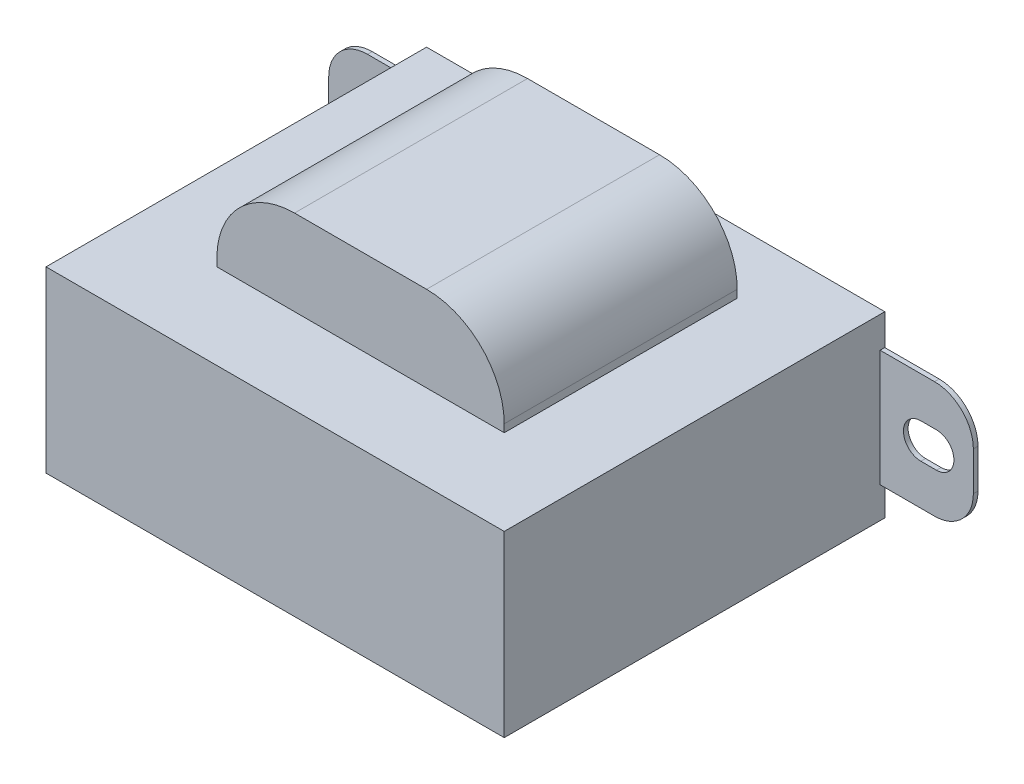
SolidWorks part; units mm, degrees
ref_plane "前视基准面" through (0, 0, 0) normal (0, 0, 1) x (1, 0, 0)
ref_plane "上视基准面" through (0, 0, 0) normal (0, 1, 0) x (1, 0, 0)
ref_plane "右视基准面" through (0, 0, 0) normal (1, 0, 0) x (0, 0, -1)
sketch "草图1" plane through (0, 0, 0) normal (0, 0, 1) x (1, 0, 0)
  line L0 (0, 78.0676) -> (0, -98.3955) construction
  line L1 (-29.5, 11.5) -> (29.5, 11.5)
  line L2 (-29.5, 11.5) -> (-29.5, -11.5)
  line L3 (-29.5, -11.5) -> (29.5, -11.5)
  line L4 (29.5, 11.5) -> (29.5, -11.5)
  line L5 (-98.6118, 0) -> (97.7467, 0) construction
  dimension "D1" = 23
  dimension "D2" = 59
extrude "拉伸1" add sketch "草图1" along normal blind 49
sketch "草图2" plane through (0, 0, 49) normal (0, 0, 1) x (1, 0, 0)
  line L1 (-8.5, 22.5) -> (8.5, 22.5)
  line L2 (-18.5, 12.5) -> (-18.5, -12.5)
  line L3 (-8.5, -22.5) -> (8.5, -22.5)
  line L4 (18.5, 12.5) -> (18.5, -12.5)
  arc A0 (-8.5, 22.5) -> (-18.5, 12.5) centre (-8.5, 12.5) ccw
  arc A1 (8.5, 22.5) -> (18.5, 12.5) centre (8.5, 12.5) cw
  arc A2 (-18.5, -12.5) -> (-8.5, -22.5) centre (-8.5, -12.5) ccw
  arc A3 (8.5, -22.5) -> (18.5, -12.5) centre (8.5, -12.5) ccw
  point P4 (0, 22.5)
  point P6 (-18.5, 0)
  point P9 (-18.5, 22.5)
  point P12 (18.5, 22.5)
  point P17 (18.5, -22.5)
  dimension "D3" = 10
  dimension "D1" = 37
  dimension "D2" = 45
extrude "拉伸2" add sketch "草图2" against normal blind 30 from offset 11 offset against normal yes
sketch "草图3" plane through (0, 0, 0) normal (0, 0, -1) x (-1, 0, 0)
  line L0 (-29.5, -11.5) -> (-29.5, 11.5) construction
  line L1 (-29.5, 7.5) -> (-36.5, 7.5)
  line L2 (-29.5, 7.5) -> (-29.5, -7.5)
  line L3 (-29.5, -7.5) -> (-36.5, -7.5)
  line L4 (-41.5, 2.5) -> (-41.5, -2.5)
  line L5 (-66.251, 0) -> (43.5792, 0) construction
  line L6 (-36.75, 0) -> (-34.75, 0) construction
  line L7 (-36.75, 2.25) -> (-34.75, 2.25)
  line L8 (-36.75, -2.25) -> (-34.75, -2.25)
  line L9 (36.75, 0) -> (34.75, 0) construction
  line L10 (0, 41.9816) -> (0, -49.4729) construction
  line L11 (36.75, 2.25) -> (34.75, 2.25)
  line L12 (36.75, -2.25) -> (34.75, -2.25)
  line L13 (41.5, 2.5) -> (41.5, -2.5)
  line L14 (29.5, -7.5) -> (36.5, -7.5)
  line L15 (29.5, 7.5) -> (29.5, -7.5)
  line L16 (29.5, 7.5) -> (36.5, 7.5)
  arc A0 (-36.75, 2.25) -> (-36.75, -2.25) centre (-36.75, 0) ccw
  arc A1 (-34.75, -2.25) -> (-34.75, 2.25) centre (-34.75, 0) ccw
  arc A2 (36.75, 2.25) -> (36.75, -2.25) centre (36.75, 0) cw
  arc A3 (34.75, -2.25) -> (34.75, 2.25) centre (34.75, 0) cw
  arc A4 (41.5, -2.5) -> (36.5, -7.5) centre (36.5, -2.5) cw
  arc A5 (36.5, 7.5) -> (41.5, 2.5) centre (36.5, 2.5) cw
  arc A6 (-36.5, -7.5) -> (-41.5, -2.5) centre (-36.5, -2.5) cw
  arc A7 (-41.5, 2.5) -> (-36.5, 7.5) centre (-36.5, 2.5) cw
  point P10 (-35.75, 0)
  point P19 (35.75, 0)
  point P31 (41.5, -7.5)
  point P34 (41.5, 7.5)
  point P37 (-41.5, -7.5)
  point P40 (-41.5, 7.5)
  dimension "D3" = 2
  dimension "D4" = 83
  dimension "D5" = 71.5
  dimension "D6" = 5
  dimension "D1" = 15
  dimension "D2" = 4.5
extrude "拉伸3" add sketch "草图3" against normal blind 0.6
